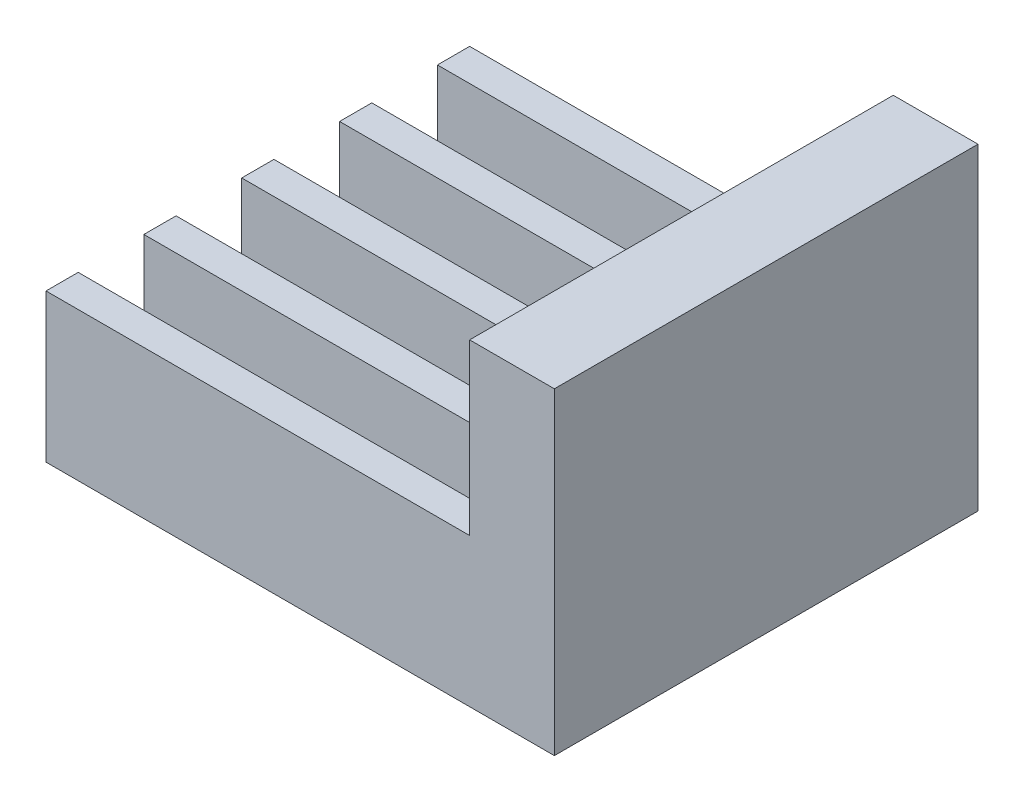
SolidWorks part; units mm, degrees
ref_plane "Front Plane" through (0, 0, 0) normal (0, 0, 1) x (1, 0, 0)
ref_plane "Top Plane" through (0, 0, 0) normal (0, 1, 0) x (1, 0, 0)
ref_plane "Right Plane" through (0, 0, 0) normal (1, 0, 0) x (0, 0, -1)
sketch "Sketch1" plane through (0, 0, 0) normal (0, 1, 0) x (1, 0, 0)
  line L1 (-63.5354, 42.4181) -> (56.4646, 42.4181)
  line L2 (-63.5354, 42.4181) -> (-63.5354, -57.5819)
  line L3 (-63.5354, -57.5819) -> (56.4646, -57.5819)
  line L4 (56.4646, 42.4181) -> (56.4646, -57.5819)
  dimension "D1" = 100
  dimension "D2" = 120
extrude "Boss-Extrude1" add sketch "Sketch1" along normal blind 75
sketch "Sketch2" plane through (0, 75, 0) normal (0, 1, 0) x (1, 0, 0)
  line L0 (-63.5354, -57.5819) -> (56.4646, -57.5819) construction
  line L1 (-63.5354, 42.4181) -> (36.4646, 42.4181)
  line L2 (-63.5354, 42.4181) -> (-63.5354, -57.5819)
  line L3 (-63.5354, -57.5819) -> (36.4646, -57.5819)
  line L4 (36.4646, 42.4181) -> (36.4646, -57.5819)
  dimension "D1" = 100
extrude "Cut-Extrude1" cut sketch "Sketch2" against normal blind 40
sketch "Sketch6" plane through (-63.5354, 0, 0) normal (-1, 0, 0) x (0, 0, 1)
  line L0 (57.5819, 35) -> (-42.4181, 35) construction
  line L1 (-34.8181, 35) -> (-19.3181, 35)
  line L2 (-34.8181, 35) -> (-34.8181, 19.5)
  line L3 (-34.8181, 19.5) -> (-19.3181, 19.5)
  line L4 (-19.3181, 35) -> (-19.3181, 19.5)
  line L5 (-19.3181, 27.25) -> (-11.7181, 27.25) construction
  line L6 (-11.7181, 35) -> (3.7819, 35)
  line L7 (-11.7181, 35) -> (-11.7181, 19.5)
  line L8 (-11.7181, 19.5) -> (3.7819, 19.5)
  line L9 (3.7819, 35) -> (3.7819, 19.5)
  line L10 (11.3819, 35) -> (26.8819, 35)
  line L11 (11.3819, 35) -> (11.3819, 19.5)
  line L12 (11.3819, 19.5) -> (26.8819, 19.5)
  line L13 (26.8819, 35) -> (26.8819, 19.5)
  line L14 (34.4819, 35) -> (49.9819, 35)
  line L15 (34.4819, 35) -> (34.4819, 19.5)
  line L16 (34.4819, 19.5) -> (49.9819, 19.5)
  line L17 (49.9819, 35) -> (49.9819, 19.5)
  line L18 (-15.5181, 27.25) -> (-15.5181, 0) construction
  line L19 (-42.4181, 0) -> (57.5819, 0) construction
  line L20 (7.5819, 35) -> (7.5819, 0) construction
  line L21 (-42.4181, 35) -> (57.5819, 35) construction
  circle A0 centre (-27.0681, 27.25) radius 5.95
  circle A1 centre (-3.9681, 27.25) radius 5.95
  circle A2 centre (42.2319, 27.25) radius 5.95
  circle A3 centre (19.1319, 27.25) radius 5.95
  point P37 (0, 0)
  dimension "D13" = 7.75
  dimension "D1" = 15.5
  dimension "D2" = 15.5
  dimension "D3" = 15.5
  dimension "D4" = 15.5
  dimension "D5" = 15.5
  dimension "D6" = 15.5
  dimension "D7" = 15.5
  dimension "D8" = 15.5
  dimension "D9" = 7.6
  dimension "D10" = 7.6
  dimension "D11" = 7.6
  dimension "D12" = 7.6
  dimension "D14" = 7.75
extrude "Cut-Extrude4" cut sketch "Sketch6" against normal blind 100 contours L11 L10 L13 L12 | L15 L14 L17 L16 | L7 L6 L9 L8 | L2 L1 L4 L3
sketch "Sketch8" plane through (-63.5354, 0, 0) normal (-1, 0, 0) x (0, 0, 1)
  line L1 (-36.6181, 19.5) -> (-17.5181, 19.5)
  line L2 (-36.6181, 19.5) -> (-36.6181, 9.5)
  line L3 (-36.6181, 9.5) -> (-17.5181, 9.5)
  line L4 (-17.5181, 19.5) -> (-17.5181, 9.5)
  line L6 (-15.5181, 35) -> (-15.5181, 0) construction
  line L7 (-19.3181, 35) -> (-11.7181, 35) construction
  line L8 (-42.4181, 0) -> (57.5819, 0) construction
  line L9 (5.5819, 9.5) -> (-13.5181, 9.5)
  line L10 (-13.5181, 19.5) -> (-13.5181, 9.5)
  line L11 (5.5819, 19.5) -> (-13.5181, 19.5)
  line L12 (5.5819, 19.5) -> (5.5819, 9.5)
  line L13 (7.5819, 35) -> (7.5819, 0) construction
  line L14 (11.3819, 35) -> (3.7819, 35) construction
  line L15 (51.7819, 9.5) -> (32.6819, 9.5)
  line L16 (32.6819, 19.5) -> (32.6819, 9.5)
  line L17 (51.7819, 19.5) -> (32.6819, 19.5)
  line L18 (51.7819, 19.5) -> (51.7819, 9.5)
  line L19 (9.5819, 19.5) -> (9.5819, 9.5)
  line L20 (9.5819, 19.5) -> (28.6819, 19.5)
  line L21 (28.6819, 19.5) -> (28.6819, 9.5)
  line L22 (9.5819, 9.5) -> (28.6819, 9.5)
  dimension "D1" = 1.8
  dimension "D2" = 10
  dimension "D3" = 19.1
extrude "Cut-Extrude5" cut sketch "Sketch8" against normal blind 100
extrude "Cut-Extrude6" cut sketch "Sketch6<3>" against normal blind 111 contours A0 | A1 | A3 | A2 region at (-63.5354, 27.25, -27.0681) region at (-63.5354, 27.25, -3.9681) region at (-63.5354, 27.25, 42.2319) region at (-63.5354, 27.25, 19.1319)
sketch "Sketch6<3>" plane through (-63.5354, 0, 0) normal (-1, 0, 0) x (0, 0, 1) same geometry as "Sketch6"
